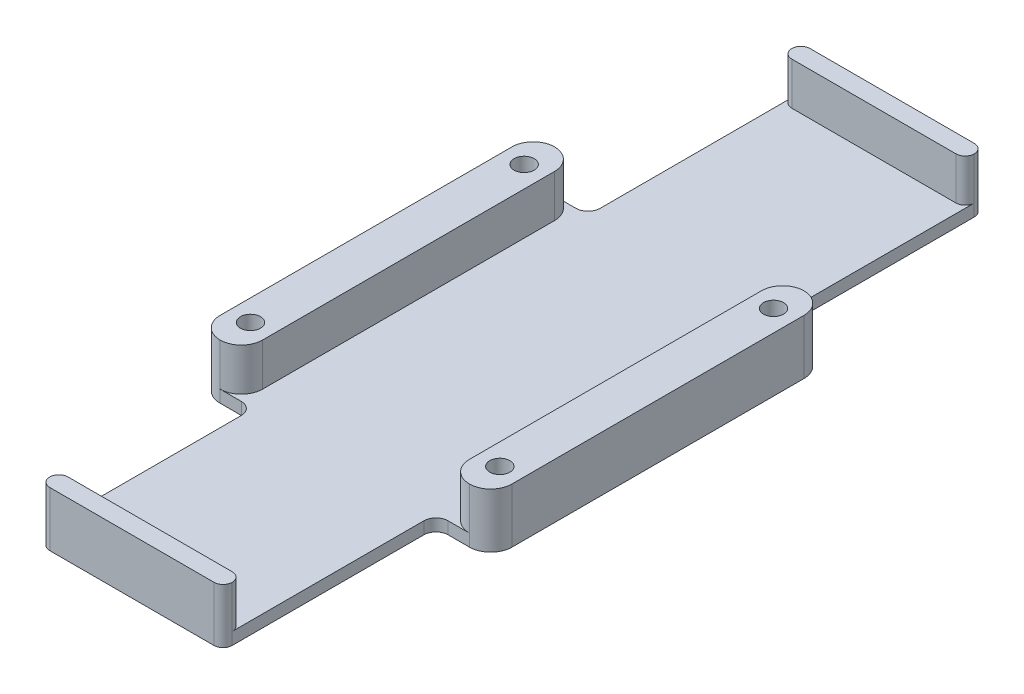
SolidWorks part; units mm, degrees
ref_plane "Спереди" through (0, 0, 0) normal (0, 0, 1) x (1, 0, 0)
ref_plane "Сверху" through (0, 0, 0) normal (0, 1, 0) x (1, 0, 0)
ref_plane "Справа" through (0, 0, 0) normal (1, 0, 0) x (0, 0, -1)
sketch "Эскиз1" plane through (0, 0, 0) normal (0, 1, 0) x (1, 0, 0)
  line L0 (0, 62.5) -> (0, -62.5) construction
  line L1 (-24, 62.5) -> (24, 62.5)
  line L2 (-24, 62.5) -> (-24, -62.5)
  line L3 (-24, -62.5) -> (24, -62.5)
  line L4 (24, 62.5) -> (24, -62.5)
  line L6 (-24, 0) -> (24, 0) construction
  point P6 (0, 0)
  dimension "D1" = 125
  dimension "D2" = 48
extrude "тело" add sketch "Эскиз1" along normal blind 2
sketch "Эскиз2" plane through (0, 2, 0) normal (0, 1, 0) x (1, 0, 0)
  line L0 (0, 62.5) -> (0, -62.5) construction
  line L1 (24, 62.5) -> (-24, 62.5) construction
  line L2 (-24, -62.5) -> (24, -62.5) construction
  line L4 (-24, 62.5) -> (-24, -62.5) construction
  line L5 (-24, 0) -> (24, 0) construction
  line L6 (24, -62.5) -> (24, 62.5) construction
  line L7 (-24, 62.5) -> (-15, 62.5)
  line L8 (-24, 62.5) -> (-24, 27.5)
  line L9 (-24, 27.5) -> (-15, 27.5)
  line L10 (-15, 62.5) -> (-15, 27.5)
  line L11 (24, 62.5) -> (15, 62.5)
  line L12 (24, 62.5) -> (24, 27.5)
  line L13 (24, 27.5) -> (15, 27.5)
  line L14 (15, 62.5) -> (15, 27.5)
  line L15 (24, -62.5) -> (15, -62.5)
  line L16 (24, -62.5) -> (24, -27.5)
  line L17 (24, -27.5) -> (15, -27.5)
  line L18 (15, -62.5) -> (15, -27.5)
  line L19 (-24, -62.5) -> (-15, -62.5)
  line L20 (-24, -62.5) -> (-24, -27.5)
  line L21 (-24, -27.5) -> (-15, -27.5)
  line L22 (-15, -62.5) -> (-15, -27.5)
  dimension "D1" = 55
  dimension "D2" = 30
extrude "пазы чтоб добраться до винтов" cut sketch "Эскиз2" against normal through all
sketch "Эскиз3" plane through (0, 2, 0) normal (0, 1, 0) x (1, 0, 0)
  line L0 (-24, 0) -> (24, 0) construction
  line L1 (-24, 27.5) -> (-24, -27.5) construction
  line L2 (24, -27.5) -> (24, 27.5) construction
  line L3 (0, 62.5) -> (0, -62.5) construction
  line L4 (15, 62.5) -> (-15, 62.5) construction
  line L5 (-15, -62.5) -> (15, -62.5) construction
  line L7 (-24, 27.5) -> (-17, 27.5)
  line L8 (-24, 27.5) -> (-24, -27.5)
  line L9 (-24, -27.5) -> (-17, -27.5)
  line L10 (-17, 27.5) -> (-17, -27.5)
  line L11 (24, 27.5) -> (17, 27.5)
  line L12 (24, 27.5) -> (24, -27.5)
  line L13 (24, -27.5) -> (17, -27.5)
  line L14 (17, 27.5) -> (17, -27.5)
  point P20 (17, 0)
  point P21 (-17, 0)
  dimension "D1" = 34
  dimension "D2" = 55
extrude "крепление к аккумулятору" add sketch "Эскиз3" along normal blind 7
sketch "Эскиз4" plane through (0, 2, 0) normal (0, 1, 0) x (1, 0, 0)
  line L0 (0, 62.5) -> (0, -62.5) construction
  line L1 (15, 62.5) -> (-15, 62.5) construction
  line L2 (-15, -62.5) -> (15, -62.5) construction
  line L4 (-15, 62.5) -> (15, 62.5)
  line L5 (-15, 62.5) -> (-15, 59.5)
  line L6 (-15, 59.5) -> (15, 59.5)
  line L7 (15, 62.5) -> (15, 59.5)
  line L8 (-15, -62.5) -> (15, -62.5)
  line L9 (-15, -62.5) -> (-15, -59.5)
  line L10 (-15, -59.5) -> (15, -59.5)
  line L11 (15, -62.5) -> (15, -59.5)
  point P14 (0, -59.5)
  point P15 (0, 59.5)
  dimension "D1" = 30
  dimension "D2" = 119
extrude "выступы фиксации аккума" add sketch "Эскиз4" along normal blind 7
sketch "Эскиз5" plane through (0, 9, 0) normal (0, 1, 0) x (1, 0, 0)
  line L0 (-24, 0) -> (24, 0) construction
  line L1 (-24, 27.5) -> (-24, -27.5) construction
  line L2 (24, -27.5) -> (24, 27.5) construction
  line L3 (-20.5, 27.5) -> (-20.5, -27.5) construction
  line L4 (15, 62.5) -> (-15, 62.5) construction
  line L5 (0, 62.5) -> (0, -62.5) construction
  line L6 (-15, -62.5) -> (15, -62.5) construction
  line L7 (-17, 27.5) -> (-24, 27.5) construction
  line L8 (-24, -27.5) -> (-17, -27.5) construction
  line L10 (24, 27.5) -> (17, 27.5) construction
  line L11 (20.5, 27.5) -> (20.5, -27.5) construction
  line L12 (17, -27.5) -> (24, -27.5) construction
  circle A0 centre (-20.5, 22.5) radius 1.65
  circle A1 centre (-20.5, -22.5) radius 1.65
  circle A2 centre (20.5, -22.5) radius 1.65
  circle A3 centre (20.5, 22.5) radius 1.65
  dimension "D1" = 3.3
  dimension "D2" = 45
extrude "отверстия для шурупов" cut sketch "Эскиз5" against normal through all
sketch "Эскиз7" plane through (0, 0, 0) normal (0, -1, 0) x (1, 0, 0)
  circle A0 centre (-20.5, 22.5) radius 3
  circle A1 centre (-20.5, -22.5) radius 3
  circle A2 centre (20.5, 22.5) radius 3
  circle A3 centre (20.5, -22.5) radius 3
  dimension "D1" = 6
extrude "углубления для шляпок" cut sketch "Эскиз7" against normal blind 4
chamfer "Фаска1" distance 1.5 angle 45 4 edges at (-20.5, 4, 20.85) (-20.5, 4, -24.15) (20.5, 4, -24.15) (20.5, 4, 20.85)
fillet "Скругление1" radius 1.5 8 edges at (-15, 5.5, 59.5) (-15, 4.5, 62.5) (15, 4.5, 62.5) (15, 5.5, 59.5) (15, 4.5, -62.5) (15, 5.5, -59.5) (-15, 5.5, -59.5) (-15, 4.5, -62.5)
fillet "Скругление2" radius 2 4 edges at (15, 1, -27.5) (-15, 1, -27.5) (-15, 1, 27.5) (15, 1, 27.5)
fillet "Скругление3" radius 3.5 8 edges at (-17, 5.5, 27.5) (-24, 4.5, 27.5) (-24, 4.5, -27.5) (-17, 5.5, -27.5) (24, 4.5, -27.5) (17, 5.5, -27.5) (17, 5.5, 27.5) (24, 4.5, 27.5)
